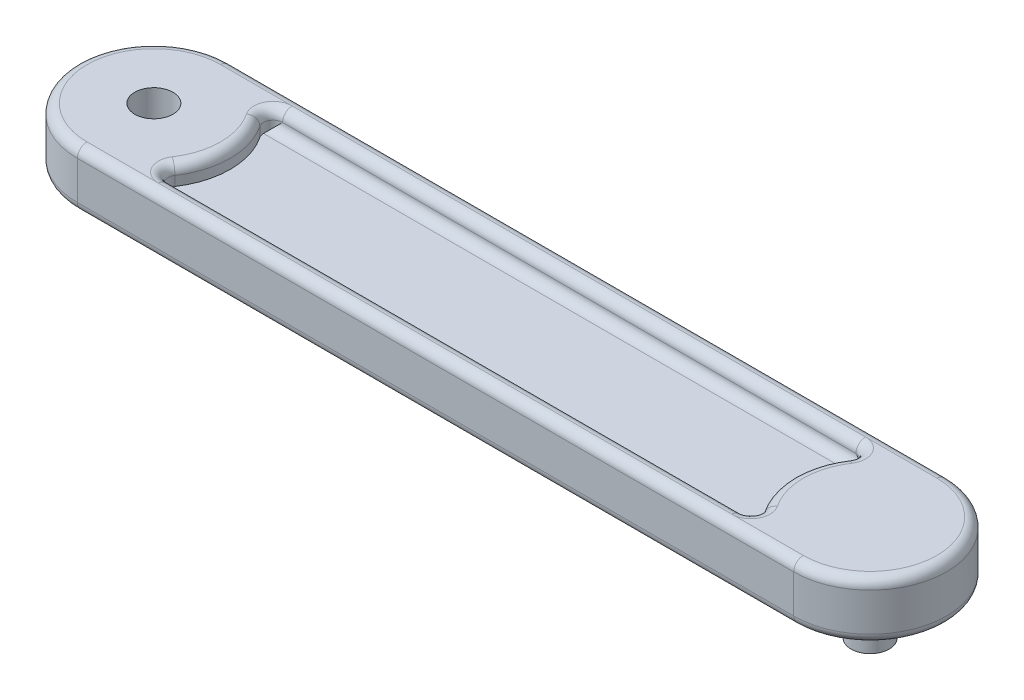
SolidWorks part; units mm, degrees
ref_plane "Piano frontale" through (0, 0, 0) normal (0, 0, 1) x (1, 0, 0)
ref_plane "Piano superiore" through (0, 0, 0) normal (0, 1, 0) x (1, 0, 0)
ref_plane "Piano destro" through (0, 0, 0) normal (1, 0, 0) x (0, 0, -1)
sketch "Sketch1" plane through (0, 0, 0) normal (0, 0, 1) x (1, 0, 0)
  line L0 (0, 8) -> (75, 8)
  line L1 (0, -8) -> (75, -8)
  arc A2 (75, 8) -> (75, -8) centre (75, 0) cw
  arc A3 (0, 8) -> (0, -8) centre (0, 0) ccw
extrude "Boss-Extrude1" add sketch "Sketch1" along normal blind 6 contours L0 A3 L1 A2
move or copy body "Body-Move/Copy1" bodies to move or copy 103 copy no rotation origin (0, 0, 11) rotation axis (-1, 0, 0) rotation angle 90
sketch "Sketch9" plane through (0, -11, 0) normal (0, -1, 0) x (1, 0, 0)
  circle A0 centre (0, 11) radius 2
sketch "Sketch11" plane through (0, -5, 0) normal (0, 1, 0) x (1, 0, 0)
  circle A1 centre (75, -11) radius 2.5
extrude "Boss-Extrude7" add sketch "Sketch11" along normal blind 5
sketch "Sketch12" plane through (0, 0, 0) normal (0, 1, 0) x (1, 0, 0)
  circle A0 centre (75, -11) radius 2.5
  circle A1 centre (75, -11) radius 2
extrude "Cut-Extrude6" cut sketch "Sketch12" against normal blind 4
extrude "Cut-Extrude7" cut sketch "Sketch9" against normal blind 10
move or copy body "Body-Move/Copy2" bodies to move or copy 117 copy no rotation origin (0, -5.5, 11) rotation axis (1, 0, 0) rotation angle 180
sketch "Sketch13" plane through (0, -6, 0) normal (0, -1, 0) x (1, 0, 0)
  line L3 (69.7085, 5) -> (63, 5)
  line L4 (63, 17) -> (69.7085, 17)
  line L5 (12, 17) -> (63, 17)
  line L7 (63, 5) -> (12, 5)
  line L9 (12, 5) -> (5.2915, 5)
  line L10 (12, 17) -> (5.2915, 17)
  arc A6 (69.7085, 17) -> (69.7085, 5) centre (75, 11) ccw
  arc A7 (5.2915, 5) -> (5.2915, 17) centre (0, 11) ccw
extrude "Cut-Extrude8" cut sketch "Sketch13" against normal blind 2
fillet "Fillet1" radius 1 12 edges at (-8, -6, 11) (37.5, -6, 19) (83, -6, 11) (37.5, -4, 5) (37.5, -6, 5) (37.5, -6, 3) (37.5, -4, 17) (37.5, -6, 17) (8, -4, 11) (8, -6, 11) (67, -4, 11) (67, -6, 11)
sketch "Sketch14" plane through (0, 0, 0) normal (0, 1, 0) x (1, 0, 0)
  line L1 (67, -5) -> (69.7085, -5)
  line L2 (67, -5) -> (5.2915, -5)
  line L4 (67, -17) -> (5.2915, -17)
  line L5 (67, -17) -> (69.7085, -17)
  arc A0 (5.2915, -17) -> (5.2915, -5) centre (0, -11) ccw
  arc A1 (69.7085, -5) -> (69.7085, -17) centre (75, -11) ccw
extrude "Cut-Extrude9" cut sketch "Sketch14" against normal blind 2
fillet "Fillet2" radius 1 14 edges at (8, 0, 11) (67, 0, 11) (-8, 0, 11) (37.5, 0, 19) (83, 0, 11) (69.7085, -1, 5) (37.5, -2, 5) (5.2915, -1, 5) (37.5, 0, 5) (5.2915, -1, 17) (37.5, -2, 17) (69.7085, -1, 17) (37.5, 0, 17) (37.5, 0, 3)
